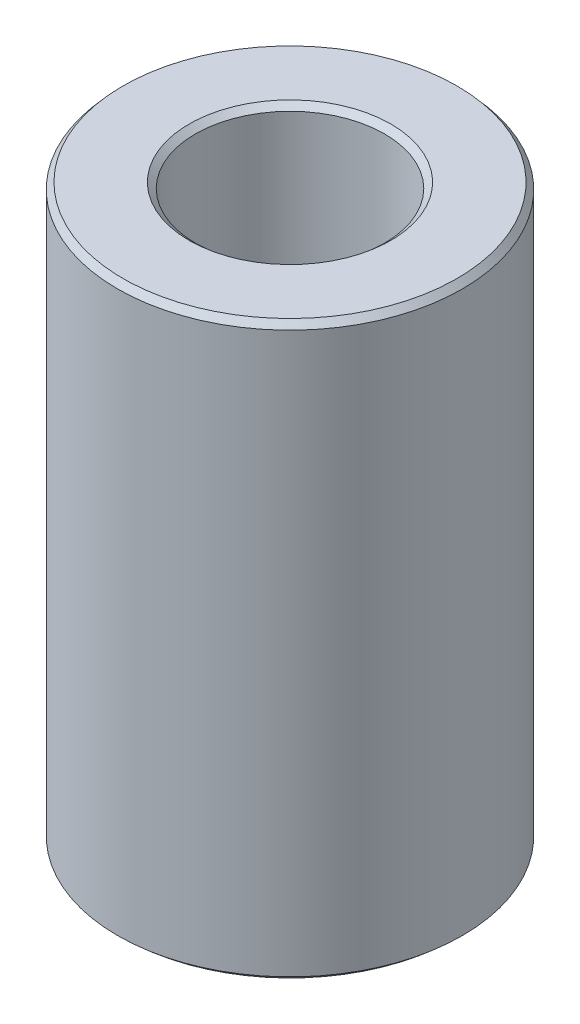
SolidWorks part; units mm, degrees
ref_plane "Front Plane" through (0, 0, 0) normal (0, 0, 1) x (1, 0, 0)
ref_plane "Top Plane" through (0, 0, 0) normal (0, 1, 0) x (1, 0, 0)
ref_plane "Right Plane" through (0, 0, 0) normal (1, 0, 0) x (0, 0, -1)
sketch "Sketch1" plane through (0, 0, 0) normal (0, 1, 0) x (1, 0, 0)
  circle A0 centre (0, 0) radius 12.5
  dimension "SLEEVE_OD" = 25
extrude "Boss-Extrude1" add sketch "Sketch1" along normal blind 41.4638
sketch "Sketch2" plane through (0, 0, 0) normal (0, 1, 0) x (1, 0, 0)
  circle A0 centre (0, 0) radius 6.8602
  dimension "BORE_D" = 13.7204
extrude "Cut-Extrude1" cut sketch "Sketch2" along normal through all
chamfer "Chamfer1" distance 0.4545 angle 40.95 4 edges at (0, 41.4638, 6.8602) (0, 0, 6.8602) (0, 0, 12.5) (0, 41.4638, 12.5) first distance on face at (0, 41.4638, 6.8602) first distance on face at (0, 0, 6.8602) first distance on face at (0, 41.4638, 12.5)
